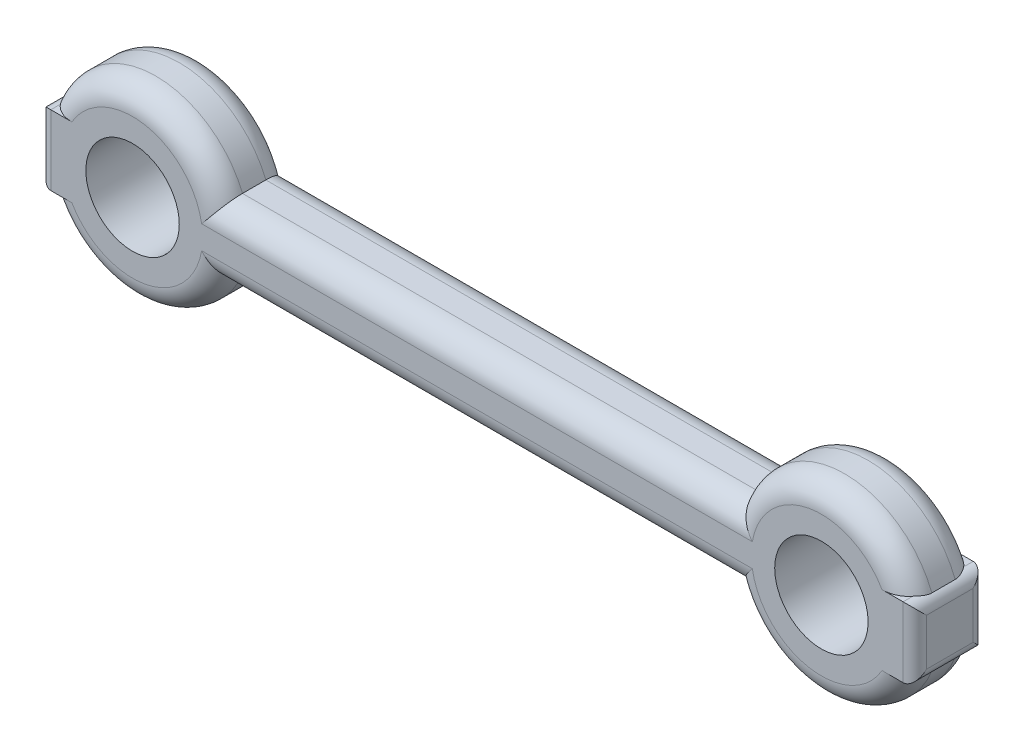
SolidWorks part; units mm, degrees
ref_plane "Front Plane" through (0, 0, 0) normal (0, 0, 1) x (1, 0, 0)
ref_plane "Top Plane" through (0, 0, 0) normal (0, 1, 0) x (1, 0, 0)
ref_plane "Right Plane" through (0, 0, 0) normal (1, 0, 0) x (0, 0, -1)
sketch "Sketch1" plane through (0, 0, 0) normal (0, 0, 1) x (1, 0, 0)
  line L4 (121.433, 98.17) -> (121.433, 68.17)
  line L7 (118.514, 98.17) -> (121.433, 98.17)
  line L8 (118.514, 68.17) -> (121.433, 68.17)
  line L9 (44.352, 98.17) -> (-176.486, 98.17)
  line L25 (-253.567, 98.17) -> (-253.567, 68.17)
  line L26 (-253.567, 68.17) -> (-250.648, 68.17)
  line L27 (-66.067, 132.2037) -> (-66.067, 24.7269) construction
  line L28 (-250.648, 98.17) -> (-253.567, 98.17)
  line L29 (-176.486, 68.17) -> (44.352, 68.17)
  arc A0 (44.352, 68.17) -> (118.514, 68.17) centre (81.433, 83.17) ccw
  arc A3 (118.514, 98.17) -> (44.352, 98.17) centre (81.433, 83.17) ccw
  circle A5 centre (81.433, 83.17) radius 20
  circle A9 centre (-213.567, 83.17) radius 20
  arc A10 (-250.648, 98.17) -> (-176.486, 98.17) centre (-213.567, 83.17) cw
  arc A11 (-176.486, 68.17) -> (-250.648, 68.17) centre (-213.567, 83.17) cw
  dimension "D3" = 80
  dimension "D4" = 187.5
  dimension "D5" = 40
  dimension "D1" = 375
  dimension "D2" = 30
extrude "Boss-Extrude1" add sketch "Sketch1" along normal blind 30
fillet "Fillet1" radius 10 12 edges at (-213.567, 43.17, 30) (81.433, 43.17, 30) (-66.067, 68.17, 30) (-213.567, 43.17, 0) (-213.567, 123.17, 0) (-213.567, 123.17, 30) (81.433, 123.17, 30) (81.433, 123.17, 0) (81.433, 43.17, 0) (-66.067, 68.17, 0) (-66.067, 98.17, 30) (-66.067, 98.17, 0)
fillet "Fillet2" radius 5 8 edges at (121.433, 68.17, 15) (121.433, 83.17, 30) (121.433, 98.17, 15) (121.433, 83.17, 0) (-253.567, 98.17, 15) (-253.567, 83.17, 30) (-253.567, 68.17, 15) (-253.567, 83.17, 0)
